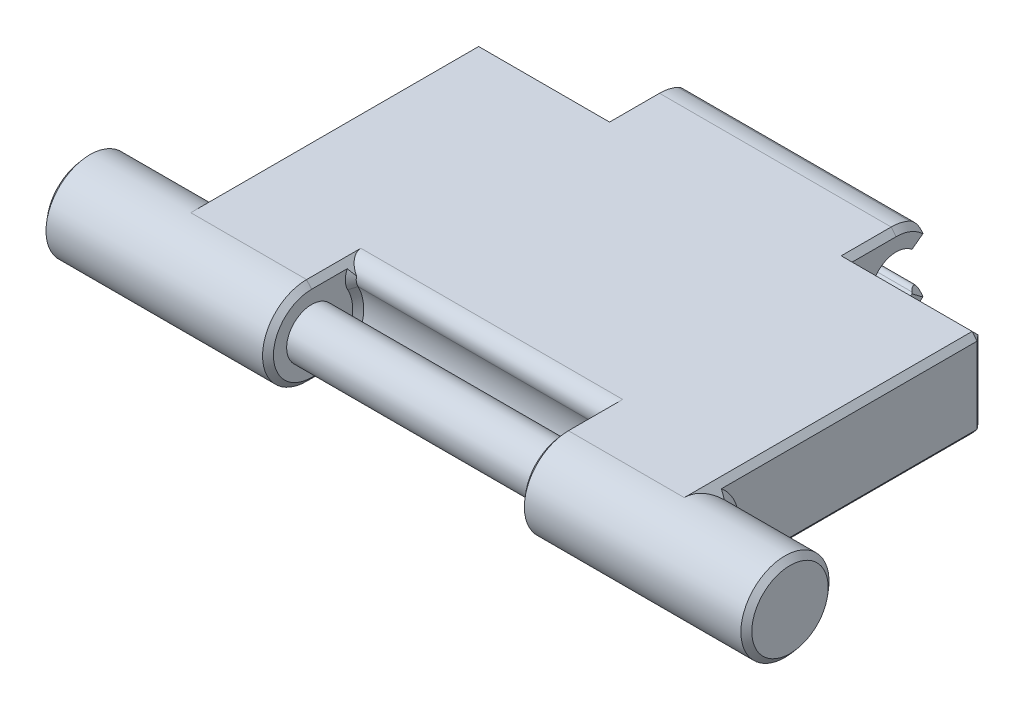
SolidWorks part; units mm, degrees
ref_plane "Front Plane" through (0, 0, 0) normal (0, 0, 1) x (1, 0, 0)
ref_plane "Top Plane" through (0, 0, 0) normal (0, 1, 0) x (1, 0, 0)
ref_plane "Right Plane" through (0, 0, 0) normal (1, 0, 0) x (0, 0, -1)
sketch "Sketch1" plane through (0, 0, 0) normal (0, 1, 0) x (1, 0, 0)
  line L1 (-5, 2.5) -> (5, 2.5)
  line L2 (-5, 2.5) -> (-5, -2.5)
  line L3 (-5, -2.5) -> (5, -2.5)
  line L4 (5, 2.5) -> (5, -2.5)
  line L5 (-5, 2.5) -> (5, -2.5) construction
  line L6 (-5, -2.5) -> (5, 2.5) construction
  point P0 (0, 0)
extrude "Boss-Extrude1" add sketch "Sketch1" along normal blind 1.5
sketch "Sketch4" plane through (0, 0, 0) normal (1, 0, 0) x (0, 0, -1)
  line L0 (-2.5, 1.5) -> (-2.5, 0) construction
  circle A0 centre (-2.5, 0.75) radius 0.75
extrude "Boss-Extrude3" add sketch "Sketch4" along normal mid plane 14
sketch "Sketch5" plane through (0, 0, 0) normal (1, 0, 0) x (0, 0, -1)
  circle A0 centre (-2.5, 0.75) radius 0.425
  circle A2 centre (-2.5, 0.75) radius 0.8
  dimension "D1" = 1.6
  dimension "D2" = 0.85
extrude "Cut-Extrude1" cut sketch "Sketch5" against normal mid plane 5
fillet "Fillet1" radius 0.25 2 edges at (0, 1.5, 2.2216) (0, 0, 2.2216)
sketch "Sketch8" plane through (0, 0, 0) normal (1, 0, 0) x (0, 0, -1)
  line L12 (3.25, 1.5) -> (2.5, 1.5)
  line L13 (2.5, 1.5) -> (2.5, 0)
  line L14 (2.5, 0) -> (3.25, 0)
  line L15 (3.5897, 1.0054) -> (3.8495, 1.2007)
  line L17 (3.8495, 0.2993) -> (3.5897, 0.4946)
  arc A4 (3.5897, 1.0054) -> (3.5897, 0.4946) centre (3.25, 0.75) ccw
  arc A12 (3.25, 0) -> (3.8495, 0.2993) centre (3.25, 0.75) ccw
  arc A13 (3.8495, 1.2007) -> (3.25, 1.5) centre (3.25, 0.75) ccw
extrude "Boss-Extrude5" add sketch "Sketch8" along normal mid plane 4.8
chamfer "Chamfer2" distance 0.1 angle 45 28 edges at (2.5, 0, 2.0383) (-2.5, 0, 2.0383) (2.5, 0.75, 3.25) (2.5, 1.5, 2.0383) (-2.5, 0.75, 3.25) (-2.5, 1.5, 2.0383) (5, 0, 0) (2.4, 0, -2.875) (3.7, 0, -2.5) (2.4, 1.5, -2.875) (3.7, 1.5, -2.5) (5, 1.5, 0) (5, 0.75, -2.5) (-2.4, 0, -2.875) (-3.7, 0, -2.5) (-5, 0, 0) (-5, 1.5, 0) (-2.4, 1.5, -2.875) (-3.7, 1.5, -2.5) (-5, 0.75, -2.5) (2.4, 0.079, -3.585) (2.4, 1.421, -3.585) (-2.4, 0.079, -3.585) (-2.4, 1.421, -3.585) (-2.4, 0.397, -3.7196) (-2.4, 1.103, -3.7196) (2.4, 0.397, -3.7196) (2.4, 1.103, -3.7196)
chamfer "Chamfer3" distance 0.1 angle 45 10 edges at (-2.5, 0.2316, 1.826) (-2.5, 1.2684, 1.826) (-2.5, 0.75, 1.7) (2.5, 0.2316, 1.826) (2.5, 1.2684, 1.826) (2.5, 0.75, 1.7) (-7, 0.75, 1.75) (7, 0.75, 1.75) (5, 0.75, 1.75) (-5, 0.75, 1.75)
fillet "Fillet3" radius 0.1 2 edges at (0, 0.4946, -3.5897) (0, 1.0054, -3.5897)
fillet "Fillet4" radius 0.25 2 edges at (0, 0.2993, -3.8495) (0, 1.2007, -3.8495)
scale "Scale1" scale about centroid uniform scaling no x scale factor 1.5 y scale factor 1.75 z scale factor 1.75
